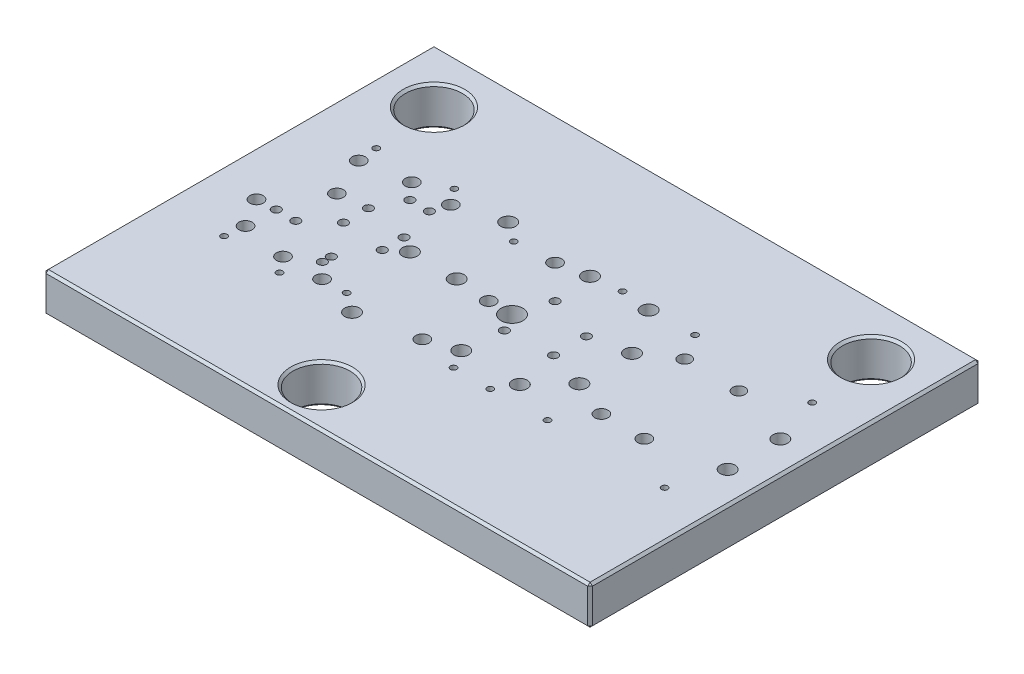
SolidWorks part; units mm, degrees
material "Plain Carbon Steel"
ref_plane "Front Plane" through (0, 0, 0) normal (0, 0, 1) x (1, 0, 0)
ref_plane "Top Plane" through (0, 0, 0) normal (0, 1, 0) x (1, 0, 0)
ref_plane "Right Plane" through (0, 0, 0) normal (1, 0, 0) x (0, 0, -1)
sketch "Sketch1" plane through (0, 0, 0) normal (0, 1, 0) x (1, 0, 0)
  line L1 (-350, -250) -> (350, -250)
  line L2 (-350, -250) -> (-350, 250)
  line L3 (-350, 250) -> (350, 250)
  line L4 (350, -250) -> (350, 250)
  line L5 (-350, -250) -> (350, 250) construction
  line L6 (-350, 250) -> (350, -250) construction
  point P0 (0, 0)
  dimension "D1" = 700
  dimension "D2" = 500
extrude "Boss-Extrude1" add sketch "Sketch1" against normal blind 50
sketch "Sketch2" plane through (0, 0, 0) normal (0, 1, 0) x (1, 0, 0)
  line L0 (350, 250) -> (-350, 250) construction
  line L1 (-350, 250) -> (-350, -250) construction
  line L2 (350, -250) -> (350, 250) construction
  line L3 (-350, -250) -> (350, -250) construction
  circle A0 centre (-280, 180) radius 36.5
  circle A1 centre (280, 180) radius 36.5
  circle A2 centre (-44, -200) radius 36.5
  dimension "D1" = 73
  dimension "D2" = 70
  dimension "D3" = 70
  dimension "D4" = 70
  dimension "D5" = 50
  dimension "D6" = 44
extrude "Cut-Extrude1" cut sketch "Sketch2" against normal up to next
chamfer "Chamfer1" distance 3 angle 45 6 edges at (280, -50, -216.5) (280, 0, -143.5) (-280, -50, -216.5) (-280, 0, -143.5) (-44, -50, 163.5) (-44, 0, 236.5)
chamfer "Chamfer2" distance 3 angle 45 12 edges at (-350, -25, -250) (-350, -25, 250) (350, -25, -250) (0, -50, -250) (-350, -50, 0) (0, -50, 250) (350, -50, 0) (350, -25, 250) (350, 0, 0) (0, 0, -250) (-350, 0, 0) (0, 0, 250)
hole_wizard "M30x2.0 Tapped Hole1" positions "Sketch5" profile "Sketch4" tap size "M30x2.0" standard "ISO" end condition through all
sketch "Sketch5" plane through (0, 0, 0) normal (0, 1, 0) x (1, 0, 0)
  point P0 (0, 0)
sketch "Sketch4" plane through (0, 0, 0) normal (1, 0, 0) x (0, 0, 1)
  line L0 (0, 0) -> (0, 50)
  line L1 (0, 50) -> (14, 50)
  line L2 (14, 50) -> (14, 0)
  line L5 (14, 0) -> (0, 0)
  line L11 (0, -6.35) -> (0, 107.95) construction
  dimension "Thru Tap Drill Dia." = 28
  dimension "Thru Tap Drill Depth" = 50
cosmetic thread "Hole Thread1"
sketch "Sketch7" plane through (0, 0, 0) normal (0, 1, 0) x (1, 0, 0)
  circle A0 centre (310, 33.75) radius 6
  circle A1 centre (310, -33.75) radius 6
  circle A2 centre (120, -33.75) radius 6
  circle A3 centre (120, 33.75) radius 6
  dimension "D1" = 12
extrude "Cut-Extrude2" cut sketch "Sketch7" against normal up to next
sketch "Sketch8" plane through (0, 0, 0) normal (0, 1, 0) x (1, 0, 0)
  circle A0 centre (222.63, -53.14) radius 8.5
  circle A1 centre (167.63, -53.14) radius 8.5
  dimension "D1" = 17
extrude "Cut-Extrude3" cut sketch "Sketch8" against normal up to next
sketch "Sketch9" plane through (0, 0, 0) normal (0, 1, 0) x (1, 0, 0)
  circle A0 centre (160.13, 61.13) radius 8
  circle A1 centre (230.13, 60.5) radius 8
  dimension "D1" = 16
extrude "Cut-Extrude4" cut sketch "Sketch9" against normal up to next
sketch "Sketch11" plane through (0, 0, 0) normal (0, 1, 0) x (1, 0, 0)
  circle A0 centre (310, -33.75) radius 9.5
  circle A1 centre (310, 33.75) radius 9.5
  circle A2 centre (120, -33.75) radius 9.5
  circle A3 centre (120, 33.75) radius 9.5
  dimension "D1" = 19
extrude "Cut-Extrude5" cut sketch "Sketch11" against normal blind 36.8
hole_wizard "M10 Tapped Hole1" positions "Sketch14" profile "Sketch13" tap size "M10" standard "ISO"
sketch "Sketch14" plane through (0, -50, 0) normal (0, -1, 0) x (-1, 0, 0)
  point P0 (-307, -94.5)
  point P3 (-123, -94.5)
  point P6 (-123, 94.5)
  point P9 (-307, 94.5)
sketch "Sketch13" plane through (307, -50, 94.5) normal (1, 0, 0) x (0, 0, -1)
  line L0 (0, 0) -> (0, 30.0537)
  line L1 (0, 30.0537) -> (4.25, 27.5)
  line L2 (4.25, 27.5) -> (4.25, 0)
  line L5 (4.25, 0) -> (0, 0)
  line L10 (0, 30.0537) -> (-4.25, 27.5) construction
  line L11 (0, -6.35) -> (0, 107.95) construction
  dimension "Tap Drill Dia." = 8.5
  dimension "Tap Drill Depth" = 27.5
  dimension "Drill Angle" = 118
cosmetic thread "Hole Thread2"
cosmetic thread "Hole Thread3"
cosmetic thread "Hole Thread4"
cosmetic thread "Hole Thread5"
hole_wizard "Ø8.0mm Dowel Hole1" positions "Sketch17" profile "Sketch16" hole size "Ø8.0" standard "ISO" end condition through all
sketch "Sketch17" plane through (0, 0, 0) normal (0, 1, 0) x (1, 0, 0)
  point P0 (290, 94.5)
  point P3 (140, 94.5)
  point P6 (290, -94.5)
  point P9 (140, -94.5)
sketch "Sketch16" plane through (290, 0, -94.5) normal (1, 0, 0) x (0, 0, 1)
  line L0 (0, 0) -> (0, 50)
  line L1 (0, 50) -> (4, 50)
  line L2 (4, 50) -> (4, 0)
  line L5 (4, 0) -> (0, 0)
  line L11 (0, -6.35) -> (0, 107.95) construction
  dimension "Thru Hole Dia." = 8
  dimension "Thru Hole Depth" = 50
hole_wizard "M8 Tapped Hole1" positions "Sketch20" profile "Sketch19" tap size "M8" standard "ISO"
sketch "Sketch20" plane through (0, -50, 0) normal (0, 1, 0) x (1, 0, 0)
  point P0 (62.13, 96.5)
  point P3 (28.13, 96.5)
  point P6 (84.13, -96.5)
  point P9 (6.13, -96.5)
sketch "Sketch19" plane through (62.13, -50, -96.5) normal (1, 0, 0) x (0, 0, -1)
  line L0 (0, 0) -> (0, 24.2929)
  line L1 (0, 24.2929) -> (3.4, 22.25)
  line L2 (3.4, 22.25) -> (3.4, 0)
  line L5 (3.4, 0) -> (0, 0)
  line L10 (0, 24.2929) -> (-3.4, 22.25) construction
  line L11 (0, -6.35) -> (0, 107.95) construction
  dimension "Tap Drill Dia." = 6.8
  dimension "Tap Drill Depth" = 22.25
  dimension "Drill Angle" = 118
cosmetic thread "Hole Thread6"
cosmetic thread "Hole Thread7"
cosmetic thread "Hole Thread8"
cosmetic thread "Hole Thread9"
hole_wizard "Ø8.0mm Dowel Hole2" positions "Sketch23" profile "Sketch22" hole size "Ø8.0" standard "ISO" end condition through all
sketch "Sketch23" plane through (0, 0, 0) normal (0, 1, 0) x (1, 0, 0)
  point P0 (68.63, -96.5)
  point P3 (21.63, -96.5)
  point P6 (45.13, 96.5)
sketch "Sketch22" plane through (68.63, 0, 96.5) normal (1, 0, 0) x (0, 0, 1)
  line L0 (0, 0) -> (0, 50)
  line L1 (0, 50) -> (4, 50)
  line L2 (4, 50) -> (4, 0)
  line L5 (4, 0) -> (0, 0)
  line L11 (0, -6.35) -> (0, 107.95) construction
  dimension "Thru Hole Dia." = 8
  dimension "Thru Hole Depth" = 50
hole_wizard "Ø11.0 (11) Diameter Hole1" positions "Sketch26" profile "Sketch25" hole size "Ø11.0" standard "ISO" end condition through all
sketch "Sketch26" plane through (0, 0, 0) normal (0, 1, 0) x (1, 0, 0)
  point P0 (71.88, -18.64)
  point P3 (12.88, -22.64)
  point P6 (71.88, 23.36)
  point P9 (12.88, 42.36)
sketch "Sketch25" plane through (71.88, 0, 18.64) normal (1, 0, 0) x (0, 0, 1)
  line L0 (0, 0) -> (0, 50)
  line L1 (0, 50) -> (5.5, 50)
  line L2 (5.5, 50) -> (5.5, 0)
  line L5 (5.5, 0) -> (0, 0)
  line L11 (0, -6.35) -> (0, 107.95) construction
  dimension "Thru Hole Dia." = 11
  dimension "Thru Hole Depth" = 50
sketch "Sketch27" plane through (0, 0, 0) normal (0, 1, 0) x (1, 0, 0)
  circle A0 centre (7.63, 92.36) radius 6
  circle A1 centre (82.63, 92.36) radius 6
  circle A2 centre (82.63, -72.64) radius 6
  circle A3 centre (7.63, -72.64) radius 6
  dimension "D1" = 12
extrude "Cut-Extrude6" cut sketch "Sketch27" against normal through all
sketch "Sketch29" plane through (0, 0, 0) normal (0, 1, 0) x (1, 0, 0)
  circle A0 centre (7.63, 92.36) radius 9.5
  circle A1 centre (82.63, 92.36) radius 9.5
  circle A2 centre (7.63, -72.64) radius 9.5
  circle A3 centre (82.63, -72.64) radius 9.5
  dimension "D1" = 19
extrude "Cut-Extrude7" cut sketch "Sketch29" against normal blind 36.8
sketch "Sketch30" plane through (0, 0, 0) normal (0, 1, 0) x (1, 0, 0)
  circle A0 centre (-29.87, 85) radius 5
  circle A1 centre (-29.87, 0) radius 5
  circle A2 centre (-29.87, -85) radius 5
  dimension "D1" = 10
extrude "Cut-Extrude8" cut sketch "Sketch30" against normal through all
sketch "Sketch31" plane through (0, 0, 0) normal (0, 1, 0) x (1, 0, 0)
  circle A0 centre (-29.87, 85) radius 8.5
  circle A1 centre (-29.87, 0) radius 8.5
  circle A2 centre (-29.87, -85) radius 8.5
  dimension "D1" = 17
extrude "Cut-Extrude9" cut sketch "Sketch31" against normal blind 39.8
hole_wizard "M8 Tapped Hole2" positions "Sketch34" profile "Sketch33" tap size "M8" standard "ISO"
sketch "Sketch34" plane through (0, -50, 0) normal (0, -1, 0) x (-1, 0, 0)
  point P0 (79.87, -97.5)
  point P3 (129.87, -97.5)
  point P6 (79.87, 97.5)
  point P9 (129.87, 97.5)
sketch "Sketch33" plane through (-79.87, -50, 97.5) normal (1, 0, 0) x (0, 0, -1)
  line L0 (0, 0) -> (0, 24.2929)
  line L1 (0, 24.2929) -> (3.4, 22.25)
  line L2 (3.4, 22.25) -> (3.4, 0)
  line L5 (3.4, 0) -> (0, 0)
  line L10 (0, 24.2929) -> (-3.4, 22.25) construction
  line L11 (0, -6.35) -> (0, 107.95) construction
  dimension "Tap Drill Dia." = 6.8
  dimension "Tap Drill Depth" = 22.25
  dimension "Drill Angle" = 118
cosmetic thread "Hole Thread10"
cosmetic thread "Hole Thread11"
cosmetic thread "Hole Thread12"
cosmetic thread "Hole Thread13"
hole_wizard "Ø8.0mm Dowel Hole3" positions "Sketch37" profile "Sketch36" hole size "Ø8.0" standard "ISO" end condition through all
sketch "Sketch37" plane through (0, 0, 0) normal (0, 1, 0) x (1, 0, 0)
  point P0 (-79.87, 81.975)
  point P3 (-129.87, -82)
sketch "Sketch36" plane through (-79.87, 0, -81.975) normal (1, 0, 0) x (0, 0, 1)
  line L0 (0, 0) -> (0, 50)
  line L1 (0, 50) -> (4, 50)
  line L2 (4, 50) -> (4, 0)
  line L5 (4, 0) -> (0, 0)
  line L11 (0, -6.35) -> (0, 107.95) construction
  dimension "Thru Hole Dia." = 8
  dimension "Thru Hole Depth" = 50
sketch "Sketch38" plane through (0, 0, 0) normal (0, 1, 0) x (1, 0, 0)
  circle A0 centre (-104.87, 100) radius 6 construction
  circle A1 centre (-104.87, -100) radius 6 construction
  circle A2 centre (-104.87, 100) radius 6
  circle A3 centre (-104.87, -100) radius 6
  circle A4 centre (-74.87, 4) radius 6 construction
  circle A5 centre (-74.87, 4) radius 6
  circle A6 centre (-134.87, 4) radius 6 construction
  circle A7 centre (-134.87, 4) radius 6
extrude "Cut-Extrude10" cut sketch "Sketch38" against normal through all
sketch "Sketch39" plane through (0, 0, 0) normal (0, 1, 0) x (1, 0, 0)
  circle A0 centre (-104.87, 100) radius 9.5
  circle A1 centre (-104.87, -100) radius 9.5
  circle A2 centre (-74.87, 4) radius 9.5
  circle A3 centre (-134.87, 4) radius 9.5
  dimension "D1" = 19
extrude "Cut-Extrude11" cut sketch "Sketch39" against normal blind 36.8
sketch "Sketch40" plane through (0, -50, 0) normal (0, -1, 0) x (1, 0, 0)
  circle A0 centre (-185.87, -82.5) radius 10 construction
  circle A1 centre (-210.87, 82.5) radius 10 construction
  circle A2 centre (-185.87, 82.5) radius 10 construction
  circle A3 centre (-160.87, 82.5) radius 10 construction
  circle A4 centre (-160.87, 33) radius 10 construction
  circle A5 centre (-210.87, 33) radius 10 construction
  circle A6 centre (-160.87, -39) radius 10 construction
  circle A7 centre (-160.87, -82.5) radius 10 construction
  circle A8 centre (-210.87, -82.5) radius 10 construction
  circle A9 centre (-210.87, -47) radius 10 construction
  circle A10 centre (-185.87, -82.5) radius 10
  circle A11 centre (-210.87, 82.5) radius 10
  circle A12 centre (-185.87, 82.5) radius 10
  circle A13 centre (-160.87, 82.5) radius 10
  circle A14 centre (-160.87, 33) radius 10
  circle A15 centre (-210.87, 33) radius 10
  circle A16 centre (-160.87, -39) radius 10
  circle A17 centre (-160.87, -82.5) radius 10
  circle A18 centre (-210.87, -82.5) radius 10
  circle A19 centre (-210.87, -47) radius 10
extrude "Cut-Extrude12" cut sketch "Sketch40" against normal blind 9.2
hole_wizard "Ø10.0 (10) Diameter Hole1" positions "Sketch44" profile "Sketch43" hole size "Ø10.0" standard "ISO" end condition through all
sketch "Sketch44" plane through (0, 0, 0) normal (0, 1, 0) x (1, 0, 0)
  point P0 (-160.87, 82.5)
  point P3 (-210.87, 82.5)
  point P6 (-160.87, -82.5)
  point P9 (-210.87, -82.5)
sketch "Sketch43" plane through (-160.87, 0, -82.5) normal (1, 0, 0) x (0, 0, 1)
  line L0 (0, 0) -> (0, 50)
  line L1 (0, 50) -> (5, 50)
  line L2 (5, 50) -> (5, 0)
  line L5 (5, 0) -> (0, 0)
  line L11 (0, -6.35) -> (0, 107.95) construction
  dimension "Thru Hole Dia." = 10
  dimension "Thru Hole Depth" = 50
sketch "Sketch45" plane through (0, 0, 0) normal (0, 1, 0) x (1, 0, 0)
  circle A0 centre (-160.87, 82.5) radius 8.5
  circle A1 centre (-210.87, 82.5) radius 8.5
  circle A2 centre (-160.87, -82.5) radius 8.5
  circle A3 centre (-210.87, -82.5) radius 8.5
  dimension "D1" = 17
extrude "Cut-Extrude13" cut sketch "Sketch45" against normal blind 33.8
hole_wizard "Ø11.0 (11) Diameter Hole2" positions "Sketch48" profile "Sketch47" hole size "Ø11.0" standard "ISO" end condition through all
sketch "Sketch48" plane through (0, 0, 0) normal (0, 1, 0) x (1, 0, 0)
  point P0 (-167.37, 61.5)
  point P3 (-192.37, 61.5)
  point P6 (-154.62, 16.36)
  point P9 (-209.87, 25.86)
  point P12 (-209.87, -6.14)
  point P15 (-179.87, -51.64)
  point P20 (-179.87, -63.14)
  point P23 (-154.62, -11.64)
sketch "Sketch47" plane through (-167.37, 0, -61.5) normal (1, 0, 0) x (0, 0, 1)
  line L0 (0, 0) -> (0, 50)
  line L1 (0, 50) -> (5.5, 50)
  line L2 (5.5, 50) -> (5.5, 0)
  line L5 (5.5, 0) -> (0, 0)
  line L11 (0, -6.35) -> (0, 107.95) construction
  dimension "Thru Hole Dia." = 11
  dimension "Thru Hole Depth" = 50
hole_wizard "M8 Tapped Hole3" positions "Sketch53" profile "Sketch52" tap size "M8" standard "ISO"
sketch "Sketch53" plane through (0, -50, 0) normal (0, -1, 0) x (-1, 0, 0)
  point P0 (160.87, -102.5)
  point P3 (210.87, -102.5)
  point P6 (160.87, 102.5)
  point P9 (210.87, 102.5)
sketch "Sketch52" plane through (-160.87, -50, 102.5) normal (1, 0, 0) x (0, 0, -1)
  line L0 (0, 0) -> (0, 24.2929)
  line L1 (0, 24.2929) -> (3.4, 22.25)
  line L2 (3.4, 22.25) -> (3.4, 0)
  line L5 (3.4, 0) -> (0, 0)
  line L10 (0, 24.2929) -> (-3.4, 22.25) construction
  line L11 (0, -6.35) -> (0, 107.95) construction
  dimension "Tap Drill Dia." = 6.8
  dimension "Tap Drill Depth" = 22.25
  dimension "Drill Angle" = 118
cosmetic thread "Hole Thread14"
cosmetic thread "Hole Thread15"
cosmetic thread "Hole Thread16"
cosmetic thread "Hole Thread17"
hole_wizard "Ø8.0mm Dowel Hole4" positions "Sketch56" profile "Sketch55" hole size "Ø8.0" standard "ISO" end condition through all
sketch "Sketch56" plane through (0, 0, 0) normal (0, 1, 0) x (1, 0, 0)
  point P0 (-176.37, 102.5)
  point P3 (-195.37, -102.5)
sketch "Sketch55" plane through (-176.37, 0, -102.5) normal (1, 0, 0) x (0, 0, 1)
  line L0 (0, 0) -> (0, 50)
  line L1 (0, 50) -> (4, 50)
  line L2 (4, 50) -> (4, 0)
  line L5 (4, 0) -> (0, 0)
  line L11 (0, -6.35) -> (0, 107.95) construction
  dimension "Thru Hole Dia." = 8
  dimension "Thru Hole Depth" = 50
sketch "Sketch57" plane through (0, 0, 0) normal (0, 1, 0) x (1, 0, 0)
  circle A0 centre (-268.87, -72.5) radius 5 construction
  circle A1 centre (-291.37, -36) radius 5 construction
  circle A2 centre (-246.37, 22) radius 5 construction
  circle A3 centre (-268.87, 72.5) radius 5 construction
  circle A4 centre (-268.87, -72.5) radius 5
  circle A5 centre (-291.37, -36) radius 5
  circle A6 centre (-246.37, 22) radius 5
  circle A7 centre (-268.87, 72.5) radius 5
extrude "Cut-Extrude14" cut sketch "Sketch57" against normal through all
sketch "Sketch58" plane through (0, 0, 0) normal (0, 1, 0) x (1, 0, 0)
  circle A0 centre (-268.87, 72.5) radius 8.5
  circle A1 centre (-246.37, 22) radius 8.5
  circle A2 centre (-291.37, -36) radius 8.5
  circle A3 centre (-268.87, -72.5) radius 8.5
  dimension "D1" = 17
extrude "Cut-Extrude15" cut sketch "Sketch58" against normal blind 36.8
hole_wizard "Ø11.0 (11) Diameter Hole3" positions "Sketch61" profile "Sketch60" hole size "Ø11.0" standard "ISO" end condition through all
sketch "Sketch61" plane through (0, 0, 0) normal (0, 1, 0) x (1, 0, 0)
  point P0 (-267.37, -34.64)
  point P3 (-242.37, -34.64)
sketch "Sketch60" plane through (-267.37, 0, 34.64) normal (1, 0, 0) x (0, 0, 1)
  line L0 (0, 0) -> (0, 50)
  line L1 (0, 50) -> (5.5, 50)
  line L2 (5.5, 50) -> (5.5, 0)
  line L5 (5.5, 0) -> (0, 0)
  line L11 (0, -6.35) -> (0, 107.95) construction
  dimension "Thru Hole Dia." = 11
  dimension "Thru Hole Depth" = 50
hole_wizard "M8 Tapped Hole4" positions "Sketch64" profile "Sketch63" tap size "M8" standard "ISO"
sketch "Sketch64" plane through (0, -50, 0) normal (0, 1, 0) x (1, 0, 0)
  point P0 (-291.37, 97.5)
  point P3 (-251.37, 97.5)
  point P6 (-251.37, -97.5)
  point P9 (-291.37, -97.5)
sketch "Sketch63" plane through (-291.37, -50, -97.5) normal (1, 0, 0) x (0, 0, -1)
  line L0 (0, 0) -> (0, 24.2929)
  line L1 (0, 24.2929) -> (3.4, 22.25)
  line L2 (3.4, 22.25) -> (3.4, 0)
  line L5 (3.4, 0) -> (0, 0)
  line L10 (0, 24.2929) -> (-3.4, 22.25) construction
  line L11 (0, -6.35) -> (0, 107.95) construction
  dimension "Tap Drill Dia." = 6.8
  dimension "Tap Drill Depth" = 22.25
  dimension "Drill Angle" = 118
cosmetic thread "Hole Thread18"
cosmetic thread "Hole Thread19"
cosmetic thread "Hole Thread20"
cosmetic thread "Hole Thread21"
hole_wizard "Ø8.0mm Dowel Hole5" positions "Sketch67" profile "Sketch66" hole size "Ø8.0" standard "ISO" end condition through all
sketch "Sketch67" plane through (0, 0, 0) normal (0, 1, 0) x (1, 0, 0)
  point P0 (-271.37, -97.5)
  point P3 (-271.37, 97.5)
sketch "Sketch66" plane through (-271.37, 0, 97.5) normal (1, 0, 0) x (0, 0, 1)
  line L0 (0, 0) -> (0, 50)
  line L1 (0, 50) -> (4, 50)
  line L2 (4, 50) -> (4, 0)
  line L5 (4, 0) -> (0, 0)
  line L11 (0, -6.35) -> (0, 107.95) construction
  dimension "Thru Hole Dia." = 8
  dimension "Thru Hole Depth" = 50
hole_wizard "M10 Tapped Hole2" positions "Sketch71" profile "Sketch69" tap size "M10" standard "ISO"
sketch "Sketch71" plane through (0, -50, 0) normal (0, -1, 0) x (-1, 0, 0)
  point P0 (-300, -190)
  point P4 (190, 190)
sketch "Sketch69" plane through (300, -50, 190) normal (1, 0, 0) x (0, 0, -1)
  line L0 (0, 0) -> (0, 30.0537)
  line L1 (0, 30.0537) -> (4.25, 27.5)
  line L2 (4.25, 27.5) -> (4.25, 0)
  line L5 (4.25, 0) -> (0, 0)
  line L10 (0, 30.0537) -> (-4.25, 27.5) construction
  line L11 (0, -6.35) -> (0, 107.95) construction
  dimension "Tap Drill Dia." = 8.5
  dimension "Tap Drill Depth" = 27.5
  dimension "Drill Angle" = 118
cosmetic thread "Hole Thread22"
cosmetic thread "Hole Thread23"
